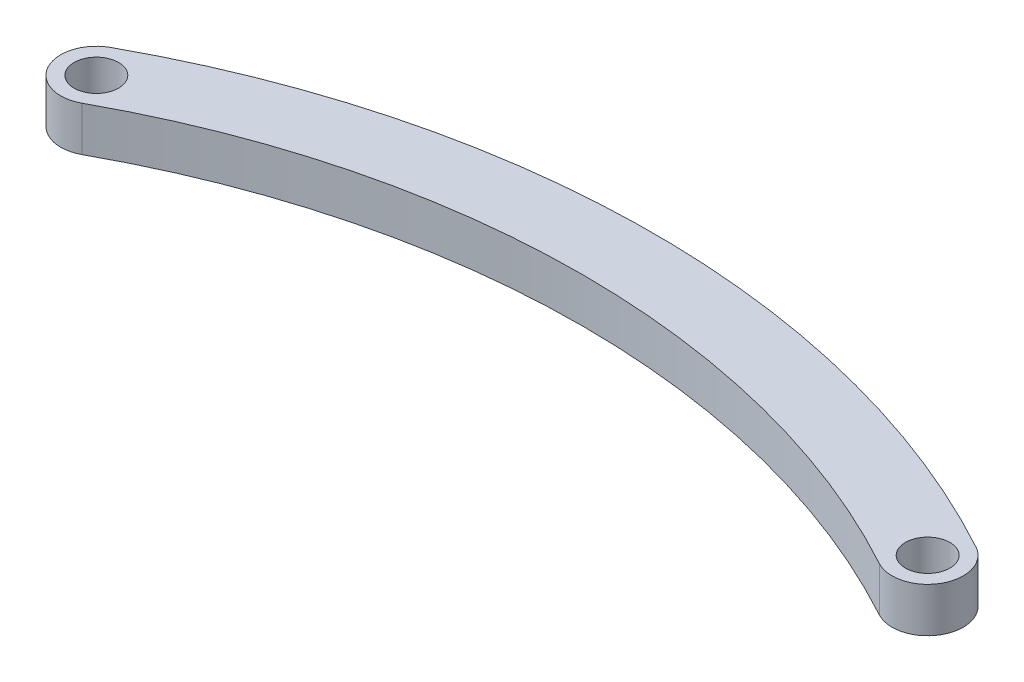
SolidWorks part; units mm, degrees
ref_plane "Front Plane" through (0, 0, 0) normal (0, 0, 1) x (1, 0, 0)
ref_plane "Top Plane" through (0, 0, 0) normal (0, 1, 0) x (1, 0, 0)
ref_plane "Right Plane" through (0, 0, 0) normal (1, 0, 0) x (0, 0, -1)
sketch "Esquisse1" plane through (0, 0, 0) normal (0, 1, 0) x (1, 0, 0)
  line L0 (-35, 0) -> (0, 0) construction
  line L1 (0, 0) -> (35, 0) construction
  circle A0 centre (-35, 0) radius 1.875
  circle A1 centre (35, 0) radius 1.875
  circle A2 centre (-35, 0) radius 3
  circle A3 centre (35, 0) radius 3
  circle A4 centre (0, -64.0625) radius 70
  circle A5 centre (0, -64.0625) radius 76
  dimension "D2" = 3.75
  dimension "D3" = 6
  dimension "D4" = 140
  dimension "D5" = 152
  dimension "D1" = 35
extrude "Boss.-Extru.1" add sketch "Esquisse1" along normal blind 3.75 contours A3 A5 A2 A4 | A2 A0 | A3 A1 region at (-32.4928, 0, 1.4872) region at (0, 0, -6.3427) region at (37.5072, 0, -1.4872)
